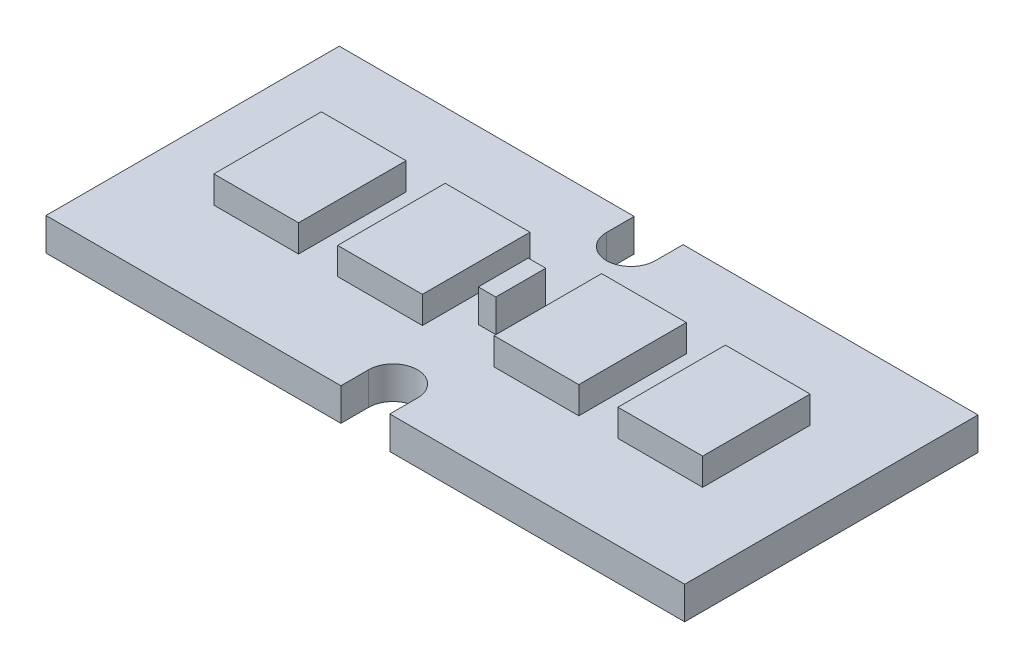
SolidWorks part; units mm, degrees
material "二氧化硅"
ref_plane "前视基准面" through (0, 0, 0) normal (0, 0, 1) x (1, 0, 0)
ref_plane "上视基准面" through (0, 0, 0) normal (0, 1, 0) x (1, 0, 0)
ref_plane "右视基准面" through (0, 0, 0) normal (1, 0, 0) x (0, 0, -1)
sketch "草图1" plane through (0, 0, 0) normal (0, 1, 0) x (1, 0, 0)
  line L1 (-9.8, 4.5) -> (9.8, 4.5)
  line L2 (-9.8, 4.5) -> (-9.8, -4.5)
  line L3 (-9.8, -4.5) -> (9.8, -4.5)
  line L4 (9.8, 4.5) -> (9.8, -4.5)
  line L5 (-9.8, 4.5) -> (9.8, -4.5) construction
  line L6 (-9.8, -4.5) -> (9.8, 4.5) construction
  point P0 (0, 0)
  dimension "D1" = 9
  dimension "D2" = 19.6
extrude "凸台-拉伸1" add sketch "草图1" along normal blind 1
sketch "草图2" plane through (0, 1, 0) normal (0, 1, 0) x (1, 0, 0)
  line L0 (-9.8, 0) -> (9.8, 0) construction
  line L1 (-9.8, 4.5) -> (-9.8, -4.5) construction
  line L2 (9.8, -4.5) -> (9.8, 4.5) construction
  line L3 (0, 0) -> (0, 7.2572) construction
  line L4 (9.8, 4.5) -> (-9.8, 4.5) construction
  line L5 (-0.75, 5.35) -> (0.75, 5.35)
  line L6 (-0.75, 5.35) -> (-0.75, 3.65)
  line L7 (-0.75, 3.65) -> (0.75, 3.65)
  line L8 (0.75, 5.35) -> (0.75, 3.65)
  line L9 (-0.75, 5.35) -> (0.75, 3.65) construction
  line L10 (-0.75, 3.65) -> (0.75, 5.35) construction
  line L11 (-0.75, -3.65) -> (0.75, -3.65)
  line L12 (0.75, -5.35) -> (0.75, -3.65)
  line L13 (-0.75, -5.35) -> (0.75, -5.35)
  line L14 (-0.75, -5.35) -> (-0.75, -3.65)
  circle A0 centre (0, 3.65) radius 0.75
  circle A1 centre (0, -3.65) radius 0.75
  point P9 (0, 4.5)
  line M4 (9.8, 4.5) -> (-9.8, 4.5)
  line M6 (-9.8, -4.5) -> (9.8, -4.5)
  dimension "D1" = 1.5
  dimension "D2" = 3.65
extrude "切除-拉伸1" cut sketch "草图2" against normal through all contours A0 L8 L6 M4 | L7 A0 | L7 A0 | A1 L11 | A1 L11 | L12 A1 L14 M6 region at (0, 1, -4.4828) region at (0, 1, -3.9683) region at (0, 1, -3.3317) region at (0, 1, 3.3317) region at (0, 1, 4.4172) region at (0, 1, 3.9683)
sketch "草图3" plane through (0, 1, 0) normal (0, 1, 0) x (1, 0, 0)
  line L0 (0, 0) -> (0, 9.7383) construction
  line L2 (-0.2688, 0.765) -> (0.2688, 0.765)
  line L3 (-0.2688, 0.765) -> (-0.2688, -0.765)
  line L4 (-0.2688, -0.765) -> (0.2688, -0.765)
  line L5 (0.2688, 0.765) -> (0.2688, -0.765)
  line L6 (-0.2688, 0.765) -> (0.2688, -0.765) construction
  line L7 (-0.2688, -0.765) -> (0.2688, 0.765) construction
sketch "草图4" plane through (0, 1, 0) normal (0, 1, 0) x (1, 0, 0)
  line L0 (0, 0) -> (-10.3499, 0)
  line L1 (0, 0) -> (0, 9.7383) construction
  line L2 (-7.5, 1.65) -> (-4.9, 1.65)
  line L3 (-7.5, 1.65) -> (-7.5, -1.65)
  line L4 (-7.5, -1.65) -> (-4.9, -1.65)
  line L5 (-4.9, 1.65) -> (-4.9, -1.65)
  line L6 (-7.5, 1.65) -> (-4.9, -1.65) construction
  line L7 (-7.5, -1.65) -> (-4.9, 1.65) construction
  line L8 (0, 0) -> (0, 6.6021) construction
  line L9 (-3.7, 1.65) -> (-1.1, 1.65)
  line L10 (-3.7, 1.65) -> (-3.7, -1.65)
  line L11 (-3.7, -1.65) -> (-1.1, -1.65)
  line L12 (-1.1, 1.65) -> (-1.1, -1.65)
  line L13 (-3.7, 1.65) -> (-1.1, -1.65) construction
  line L14 (-3.7, -1.65) -> (-1.1, 1.65) construction
  line L15 (3.7, -1.65) -> (1.1, -1.65)
  line L16 (1.1, 1.65) -> (1.1, -1.65)
  line L17 (3.7, 1.65) -> (1.1, 1.65)
  line L18 (3.7, 1.65) -> (3.7, -1.65)
  line L19 (7.5, -1.65) -> (4.9, -1.65)
  line L20 (4.9, 1.65) -> (4.9, -1.65)
  line L21 (7.5, 1.65) -> (4.9, 1.65)
  line L22 (7.5, 1.65) -> (7.5, -1.65)
  point P3 (-6.2, 0)
  point P10 (-2.4, 0)
  dimension "D1" = 7.5
  dimension "D2" = 3.3
  dimension "D3" = 2.6
  dimension "D4" = 3.3
  dimension "D5" = 1.2
extrude "凸台-拉伸2" add sketch "草图4" along normal blind 0.83 contours L5 L2 L3 L0 | L5 L0 L3 L4 | L12 L9 L10 L0 | L12 L0 L10 L11 | L18 L17 L16 L15 | L22 L21 L20 L19 region at (-2.4, 1, 0.825) region at (-2.4, 1, -0.825) region at (-6.2, 1, 0.825) region at (-6.2, 1, -0.825) region at (2.4, 1, 0) region at (6.2, 1, 0)
extrude "凸台-拉伸3" add sketch "草图3" along normal blind 1
